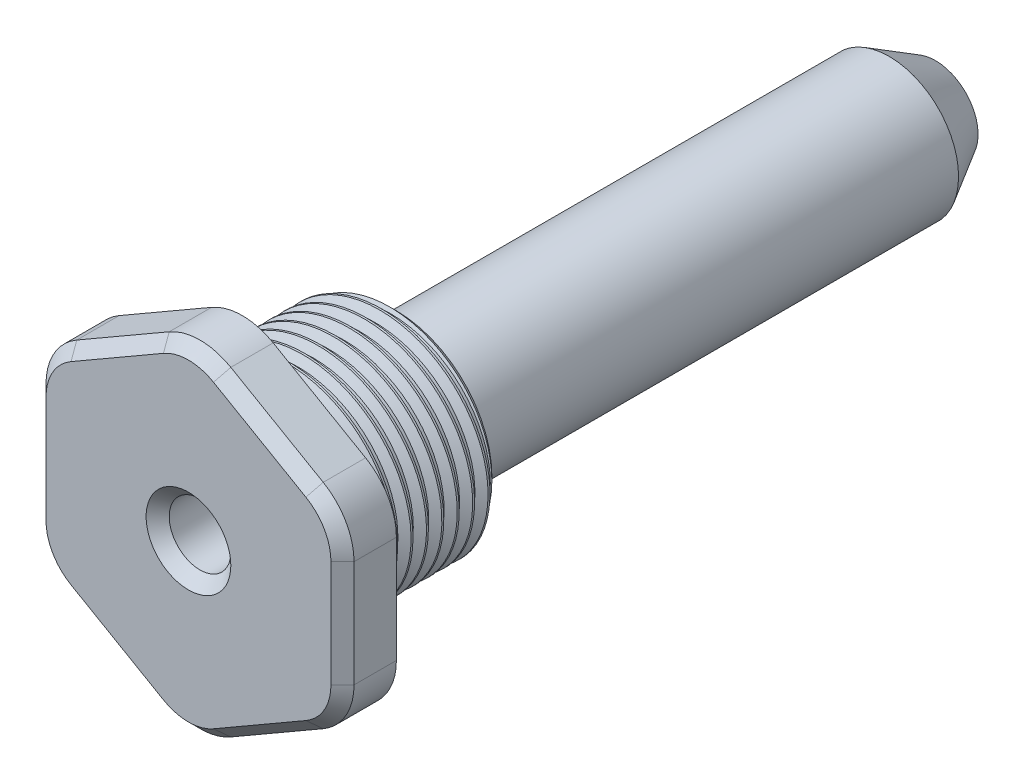
SolidWorks part; units mm, degrees
ref_plane "Front Plane" through (0, 0, 0) normal (0, 0, 1) x (1, 0, 0)
ref_plane "Top Plane" through (0, 0, 0) normal (0, 1, 0) x (1, 0, 0)
ref_plane "Right Plane" through (0, 0, 0) normal (1, 0, 0) x (0, 0, -1)
sketch "Sketch1" plane through (0, 0, 0) normal (0, 0, 1) x (1, 0, 0)
  circle A0 centre (0, 0) radius 6.95
  dimension "D1" = 13.9
extrude "Boss-Extrude1" add sketch "Sketch1" along normal blind 10
chamfer "Chamfer1" distance 0.75 angle 45 1 edges at (6.95, 0, 0)
sketch "Sketch2" plane through (0, 0, 10) normal (0, 0, 1) x (1, 0, 0)
  circle A0 centre (0, 0) radius 6.95 construction
  circle A1 centre (0, 0) radius 6.95
curve "Helix/Spiral1" pitch 1 height 11 radius 6.95 centre (0, 0, 10) axis (0, 0, -1) start towards (1, 0, 0)
sketch "Sketch3" plane through (0, 0, 0) normal (0, 1, 0) x (1, 0, 0)
  line L0 (6.1922, -10.4375) -> (7.1083, -10.4375) construction
  line L1 (7.0583, -9.9375) -> (6.1922, -9.4375) construction
  line L2 (6.1922, -9.4375) -> (6.1922, -11.4375) construction
  line L3 (6.1922, -10.4375) -> (7.0583, -9.9375) construction
  line L4 (7.0583, -10.9375) -> (6.1922, -11.4375) construction
  line L5 (6.1922, -10.4375) -> (7.0583, -10.9375) construction
  line L6 (6.95, -10.875) -> (6.95, -11) construction
  line L7 (6.4087, -10.3125) -> (6.4087, -10.5625)
  line L8 (6.4087, -10.5625) -> (6.95, -10.875)
  line L9 (6.95, -10.875) -> (6.95, -10)
  line L10 (6.95, -10) -> (6.4087, -10.3125)
  circle A0 centre (6.4809, -9.9375) radius 0.2887 construction
  dimension "D1" = 1
  dimension "D2" = 0.125
  dimension "D3" = 0.25
sweep "Cut-Sweep1" cut profiles "Sketch3" path "Helix/Spiral1"
sketch "Sketch4" plane through (0, 0, 10) normal (0, 0, 1) x (1, 0, 0)
  line L1 (0, 11.547) -> (-10, 5.7735)
  line L2 (-10, 5.7735) -> (-10, -5.7735)
  line L3 (-10, -5.7735) -> (0, -11.547)
  line L4 (0, -11.547) -> (10, -5.7735)
  line L5 (10, -5.7735) -> (10, 5.7735)
  line L6 (10, 5.7735) -> (0, 11.547)
  circle A0 centre (0, 0) radius 10 construction
  dimension "D1" = 20
extrude "Boss-Extrude2" add sketch "Sketch4" along normal blind 3.5
fillet "Fillet1" radius 4 6 edges at (10, -5.7735, 11.75) (0, -11.547, 11.75) (-10, -5.7735, 11.75) (-10, 5.7735, 11.75) (0, 11.547, 11.75) (10, 5.7735, 11.75)
chamfer "Chamfer3" distance 0.75 angle 45 12 edges at (0, -10.9282, 13.5) (-5, -8.6603, 13.5) (-9.4641, -5.4641, 13.5) (-10, 0, 13.5) (-9.4641, 5.4641, 13.5) (-5, 8.6603, 13.5) (0, 10.9282, 13.5) (5, 8.6603, 13.5) (9.4641, 5.4641, 13.5) (10, 0, 13.5) (9.4641, -5.4641, 13.5) (5, -8.6603, 13.5)
sketch "Sketch5" plane through (0, 0, 0) normal (0, 0, -1) x (-1, 0, 0)
  circle A0 centre (0, 0) radius 4.5
  dimension "D1" = 9
extrude "Boss-Extrude3" add sketch "Sketch5" along normal blind 35
fillet "Fillet2" radius 0.5 1 edges at (4.5, 0, 0)
sketch "Sketch6" plane through (0, 0, 13.5) normal (0, 0, 1) x (1, 0, 0)
  circle A0 centre (0, 0) radius 2
  dimension "D1" = 4
extrude "Cut-Extrude1" cut sketch "Sketch6" against normal blind 30
chamfer "Chamfer4" distance 3.4 angle 30 1 edges at (2, 0, -16.5) first distance on face at (2, 0, -16.5)
chamfer "Chamfer5" distance 3 angle 30 1 edges at (-4.5, 0, -35) first distance on face at (4.5, 0, -0.5)
chamfer "Chamfer6" distance 0.75 angle 45 1 edges at (2, 0, 13.5)
equation "\"D2@Sketch3\"=1/8"
equation "\"D3@Sketch3\"=1/4"
